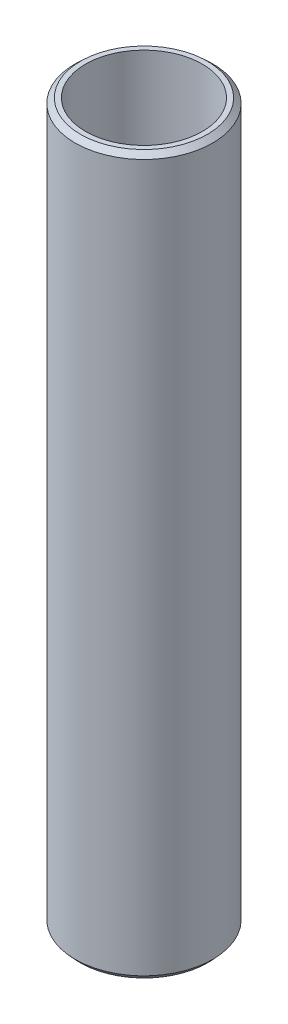
SolidWorks part; units mm, degrees
ref_plane "Front Plane" through (0, 0, 0) normal (0, 0, 1) x (1, 0, 0)
ref_plane "Top Plane" through (0, 0, 0) normal (0, 1, 0) x (1, 0, 0)
ref_plane "Right Plane" through (0, 0, 0) normal (1, 0, 0) x (0, 0, -1)
sketch "Sketch1" plane through (0, 0, 0) normal (0, 1, 0) x (1, 0, 0)
  circle A0 centre (0, 0) radius 57.5
  dimension "SHAFT_OD" = 115
extrude "Boss-Extrude1" add sketch "Sketch1" along normal blind 600
sketch "Sketch2" plane through (0, 0, 0) normal (0, 1, 0) x (1, 0, 0)
  circle A0 centre (0, 0) radius 48.8698
  dimension "BORE_D" = 97.7396
extrude "Cut-Extrude1" cut sketch "Sketch2" along normal through all
chamfer "Chamfer1" distance 4.0735 angle 47.5 2 edges at (0, 600, 57.5) (0, 0, 57.5) first distance on face at (0, 600, 57.5) first distance on face at (0, 0, 48.8698)
